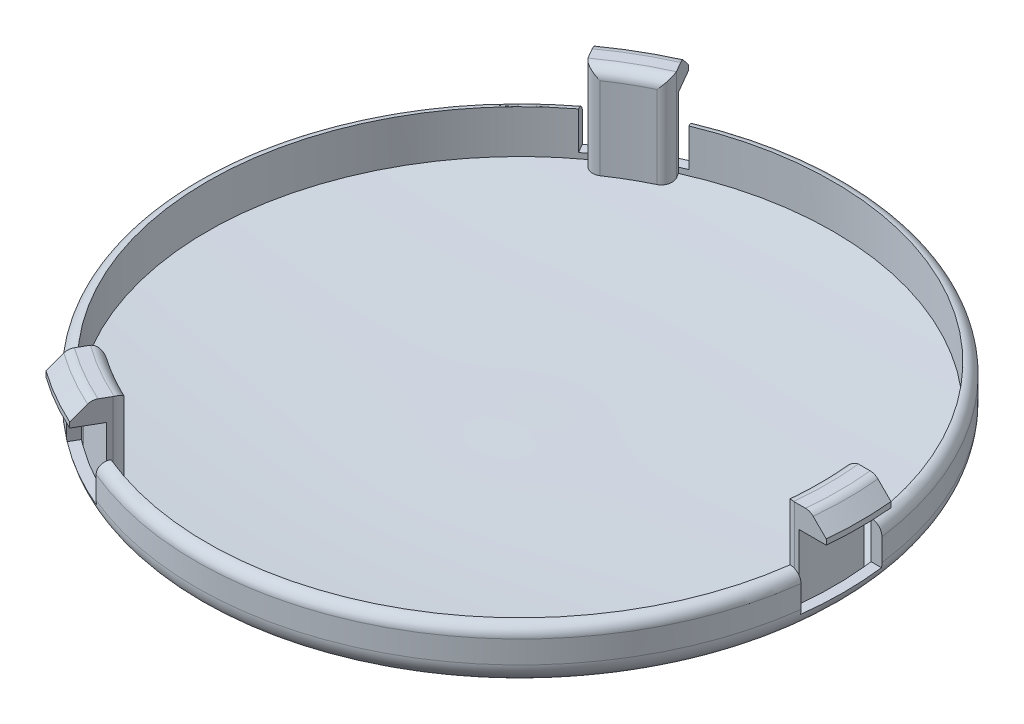
SolidWorks part; units mm, degrees
ref_plane "Front Plane" through (0, 0, 0) normal (0, 0, 1) x (1, 0, 0)
ref_plane "Top Plane" through (0, 0, 0) normal (0, 1, 0) x (1, 0, 0)
ref_plane "Right Plane" through (0, 0, 0) normal (1, 0, 0) x (0, 0, -1)
sketch "Sketch1" plane through (0, 0, 0) normal (0, 0, 1) x (1, 0, 0)
  line L0 (0, 0) -> (-7.4556, 0) construction
  line L1 (0, 0) -> (0, 2) construction
  line L2 (0, 2) -> (0, 6) construction
  line L3 (-30, 1) -> (-30, 6)
  line L4 (-30, 6) -> (-29, 6)
  line L5 (-29, 6) -> (-29, 2)
  line L6 (0, 0) -> (0, 1) construction
  line L7 (-29, 0.9962) -> (-29, 0.9962)
  line L8 (-29, 0.9962) -> (-29, 0.9962)
  line L9 (-29, 0.9962) -> (-29, 0.9962)
  line L10 (-0.9999, -0.0166) -> (-0.9999, -0.0166)
  line L11 (0, 0) -> (0, -2.8188) construction
  line L12 (0, 1) -> (0, -0.0002)
  arc A0 (-29, 2) -> (0, 1) centre (-5.0361, 275.9539) ccw
  arc A1 (-30, 1.0852) -> (0, -0.0002) centre (-5.0361, 275.9539) ccw
  arc A2 (-29, 0.9962) -> (-0.9999, -0.0166) centre (-5.0361, 275.9539) ccw construction
  dimension "D10" = 275
  dimension "D1" = 2
  dimension "D2" = 4
  dimension "D3" = 5
  dimension "D4" = 4
  dimension "D5" = 1
  dimension "D6" = 1
  dimension "D7" = 30
  dimension "D8" = 6
  dimension "D11" = 0
  dimension "D9" = 1
revolve "Revolve1" add sketch "Sketch1" angle 360 about L2 region at (-16.696, 1.1493, 0)
sketch "Sketch2" plane through (0, 6, 0) normal (0, 1, 0) x (1, 0, 0)
  line L0 (0, 0) -> (43.4788, 0) construction
  line L1 (0, 0) -> (-26.0352, 45.0943) construction
  line L2 (0, 0) -> (-18.4663, -31.9845) construction
  line L3 (28.7565, -3.75) -> (29.7647, -3.75)
  line L4 (28.7565, 3.75) -> (29.7647, 3.75)
  line L5 (-11.1307, -26.7789) -> (-11.6348, -27.652)
  line L6 (0, 3.75) -> (43.4788, 3.75) construction
  line L7 (0, -3.75) -> (43.4788, -3.75) construction
  line L8 (-17.6259, -23.0289) -> (-18.1299, -23.902)
  line L9 (-17.6259, 23.0289) -> (-18.1299, 23.902)
  line L10 (-11.1307, 26.7789) -> (-11.6348, 27.652)
  circle A0 centre (0, 0) radius 30 construction
  circle A1 centre (0, 0) radius 29 construction
  arc A2 (-15, 25.9808) -> (-15, -25.9808) centre (0, 0) ccw
  arc A3 (-14.5, 25.1147) -> (-14.5, -25.1147) centre (0, 0) ccw
  arc A4 (28.7565, -3.75) -> (28.7565, 3.75) centre (0, 0) ccw
  arc A5 (29.7647, -3.75) -> (29.7647, 3.75) centre (0, 0) ccw
  arc A6 (-18.1299, -23.902) -> (-11.6348, -27.652) centre (0, 0) ccw
  arc A7 (-17.6259, -23.0289) -> (-11.1307, -26.7789) centre (0, 0) ccw
  arc A8 (-11.6348, 27.652) -> (-18.1299, 23.902) centre (0, 0) ccw
  arc A9 (-11.1307, 26.7789) -> (-17.6259, 23.0289) centre (0, 0) ccw
  point P31 (0, 0)
  circle M10 centre (0, 0) radius 29
  circle M11 centre (0, 0) radius 30
  dimension "D1" = 120
  dimension "D2" = 120
  dimension "D3" = 3.75
  dimension "D4" = 3.75
  dimension "D5" = 3
extrude "Cut-Extrude1" cut sketch "Sketch2" against normal blind 3.5 contours L4 L3 M10 M11 | L8 L5 M10 M11 | L10 L9 M10 M11 region at (29.4202, 6, 0) region at (-14.7101, 6, 25.4786) region at (-14.7101, 6, -25.4786)
fillet "Fillet1" radius 2 1 edges at (0, 1.0852, -30)
fillet "Fillet2" radius 1 3 edges at (15, 6, 25.9808) (-30, 6, 0) (15, 6, -25.9808)
ref_plane "Plane1" through (0, 10.5, 0) normal (0, 1, 0) x (1, 0, 0)
sketch "Sketch3" plane through (0, 10.5, 0) normal (0, 1, 0) x (1, 0, 0)
  line L0 (0, 0) -> (37.2008, 0) construction
  line L1 (0, 0) -> (-21.5287, 37.2889) construction
  line L2 (0, 0) -> (-16.9407, -29.3421) construction
  line L3 (-11.0699, 25.1736) -> (-11.8241, 26.48)
  line L4 (-16.266, 22.1736) -> (-17.0203, 23.48)
  line L5 (27.3359, 3) -> (28.8444, 3)
  line L6 (2.5981, 1.5) -> (-18.9307, 38.7889) construction
  line L7 (-2.5981, -1.5) -> (-24.1268, 35.7889) construction
  line L8 (27.3359, -3) -> (28.8444, -3)
  line L9 (-11.0699, -25.1736) -> (-11.8241, -26.48)
  line L10 (-16.266, -22.1736) -> (-17.0203, -23.48)
  circle A0 centre (0, 0) radius 29 construction
  arc A1 (-14.5, -25.1147) -> (29, 0) centre (0, 0) ccw
  arc A2 (-13.75, -23.8157) -> (27.5, 0) centre (0, 0) ccw
  arc A3 (-11.0699, 25.1736) -> (-16.266, 22.1736) centre (0, 0) ccw
  arc A4 (-11.8241, 26.48) -> (-17.0203, 23.48) centre (0, 0) ccw
  arc A5 (28.8444, -3) -> (28.8444, 3) centre (0, 0) ccw
  arc A6 (27.3359, -3) -> (27.3359, 3) centre (0, 0) ccw
  arc A7 (-17.0203, -23.48) -> (-11.8241, -26.48) centre (0, 0) ccw
  arc A8 (-16.266, -22.1736) -> (-11.0699, -25.1736) centre (0, 0) ccw
  point P30 (0, 0)
  dimension "D3" = 1.5
  dimension "D1" = 120
  dimension "D2" = 120
  dimension "D4" = 3
  dimension "D5" = 3
  dimension "D6" = 3
extrude "Boss-Extrude1" add sketch "Sketch3" against normal up to next contours L3 A4 L4 A3 | A6 A2 L8 A1 A5 L5 | A8 L10 A7 A1 L9 A2 region at (-14.0983, 10.5, -24.4191) region at (28.1967, 10.5, 0) region at (-14.0983, 10.5, 24.4191)
sketch "Sketch4" plane through (0, 10.5, 0) normal (0, 1, 0) x (1, 0, 0)
  line L0 (0, 0) -> (29.9559, 0) construction
  line L1 (0, 0) -> (-18.8742, 32.6911) construction
  line L2 (0, 0) -> (-19.2298, -33.3071) construction
  line L3 (-18.2765, 25.6558) -> (-17.0203, 23.48)
  line L4 (-13.0803, 28.6558) -> (-11.8241, 26.48)
  line L5 (-13.0803, 28.6558) -> (-18.2765, 25.6558) construction
  line L6 (31.3568, -3) -> (28.8444, -3)
  line L7 (31.3568, 3) -> (28.8444, 3)
  line L8 (-18.2765, -25.6558) -> (-17.0203, -23.48)
  line L9 (-13.0803, -28.6558) -> (-11.8241, -26.48)
  arc A0 (29.7202, -3.75) -> (29.7202, 3.75) centre (0, 0) ccw construction
  arc A1 (-11.0699, 25.1736) -> (-16.266, 22.1736) centre (0, 0) ccw construction
  arc A2 (-11.0699, 25.1736) -> (-16.266, 22.1736) centre (0, 0) ccw construction
  arc A3 (-13.0803, 28.6558) -> (-18.2765, 25.6558) centre (0, 0) ccw
  arc A4 (-11.8241, 26.48) -> (-17.0203, 23.48) centre (0, 0) ccw construction
  arc A5 (-11.8241, 26.48) -> (-17.0203, 23.48) centre (0, 0) ccw
  arc A6 (28.8444, -3) -> (28.8444, 3) centre (0, 0) ccw
  arc A7 (31.3568, -3) -> (31.3568, 3) centre (0, 0) ccw
  arc A8 (-17.0203, -23.48) -> (-11.8241, -26.48) centre (0, 0) ccw
  arc A9 (-18.2765, -25.6558) -> (-13.0803, -28.6558) centre (0, 0) ccw
  point P12 (2.5981, 1.5)
  point P13 (-16.2761, 34.1911)
  point P14 (-2.5981, -1.5)
  point P15 (-21.4723, 31.1911)
  point P31 (0, 0)
  dimension "D3" = 4
  dimension "D1" = 120
  dimension "D2" = 120
  dimension "D4" = 6
  dimension "D5" = 3
extrude "Boss-Extrude2" add sketch "Sketch4" against normal blind 2
chamfer "Chamfer1" distance 1.5 angle 45 3 edges at (-15.75, 10.5, -27.2798) (31.5, 10.5, 0) (-15.75, 10.5, 27.2798)
fillet "Fillet3" radius 1 12 edges at (-11.0699, 6.1865, 25.1736) (-16.266, 6.1865, 22.1736) (-11.0699, 6.1865, -25.1736) (-16.266, 6.1865, -22.1736) (27.3359, 6.1865, -3) (27.3359, 6.1865, 3) (30, 10.5, 0) (-15, 10.5, 25.9808) (-15, 10.5, -25.9808) (-13.75, 10.5, -23.8157) (-13.75, 10.5, 23.8157) (27.5, 10.5, 0)
